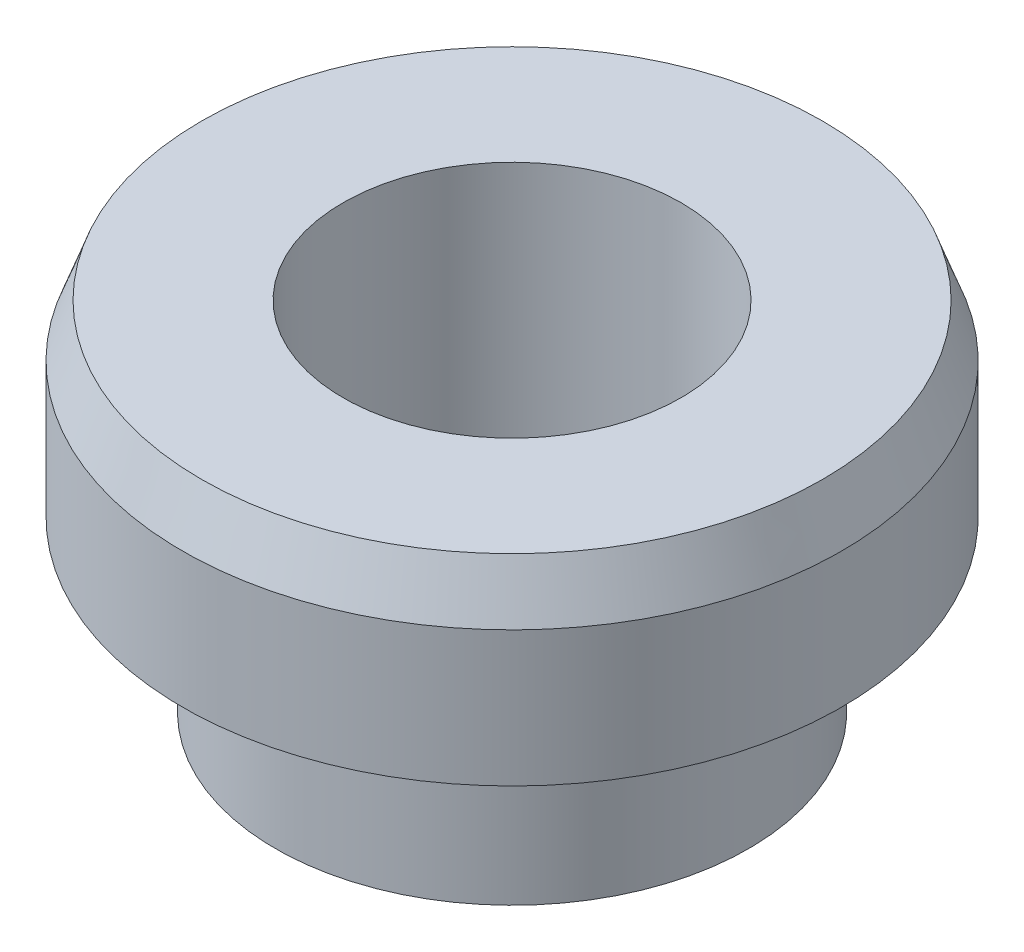
SolidWorks part; units mm, degrees
ref_plane "Front Plane" through (0, 0, 0) normal (0, 0, 1) x (1, 0, 0)
ref_plane "Top Plane" through (0, 0, 0) normal (0, 1, 0) x (1, 0, 0)
ref_plane "Right Plane" through (0, 0, 0) normal (1, 0, 0) x (0, 0, -1)
sketch "Sketch1" plane through (0, 0, 0) normal (0, 0, 1) x (1, 0, 0)
  line L0 (0, 0) -> (0, 5.4195) construction
  line L3 (9.75, 8.9092) -> (9.75, 4.9092)
  line L4 (9.75, 4.9092) -> (7, 4.9092)
  line L5 (7, 4.9092) -> (7, -0.0908)
  line L6 (7, -0.0908) -> (5, -0.0908)
  line L7 (5, -0.0908) -> (5, 10.4618)
  line L8 (5, 10.4618) -> (9.1849, 10.4618)
  line L10 (9.1849, 10.4618) -> (9.75, 8.9092)
  dimension "D1" = 14
  dimension "D3" = 110
  dimension "D4" = 5
  dimension "D5" = 19.5
  dimension "D6" = 4
revolve "Revolve1" add sketch "Sketch1" angle 360 about L0
